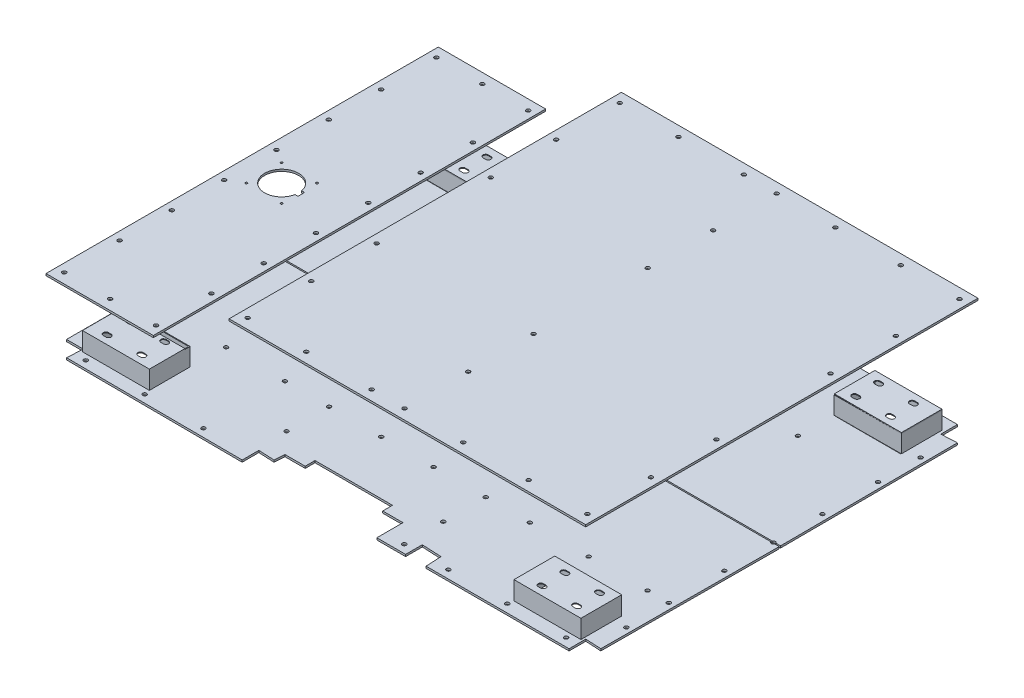
SolidWorks part; units mm, degrees
ref_plane "Front Plane" through (0, 0, 0) normal (0, 0, 1) x (1, 0, 0)
ref_plane "Top Plane" through (0, 0, 0) normal (0, 1, 0) x (1, 0, 0)
ref_plane "Right Plane" through (0, 0, 0) normal (1, 0, 0) x (0, 0, -1)
sketch "Sketch2" plane through (0, 422.0595, 0) normal (0, 1, 0) x (1, 0, 0)
  line L1 (715.0951, -383.2952) -> (690.8951, -384.4952)
  line L2 (690.8951, -384.4952) -> (690.8951, -359.0952)
  line L3 (690.8951, -359.0952) -> (466.2951, -359.0952)
  line L4 (466.2951, -359.0952) -> (465.0951, -383.2952)
  line L5 (465.0951, -383.2952) -> (440.8951, -384.4952)
  line L6 (440.8951, -384.4952) -> (440.8951, -359.0952)
  line L7 (440.8951, -359.0952) -> (390.8951, -359.0952)
  line L8 (390.8951, -359.0952) -> (390.8951, -399.0952)
  line L9 (410.8951, -483.6952) -> (410.8951, -384.4952) construction
  line L10 (390.8951, -399.0952) -> (216.2951, -399.0952)
  line L11 (196.2951, -384.4952) -> (196.2951, -483.6952) construction
  line L12 (216.2951, -399.0952) -> (215.0951, -383.2952)
  line L13 (215.0951, -383.2952) -> (190.8951, -384.4952)
  line L14 (190.8951, -384.4952) -> (190.8951, -359.0952)
  line L15 (190.8951, -359.0952) -> (-84.9049, -360.2952)
  line L16 (-84.9049, -360.2952) -> (-83.7049, -384.4952)
  line L17 (-83.7049, -384.4952) -> (-109.1049, -384.4952)
  line L18 (-109.1049, -384.4952) -> (-109.1049, -933.6952)
  line L19 (-109.1049, -933.6952) -> (-109.1049, -384.4952) construction
  line L20 (715.0951, -383.2952) -> (716.2951, -659.0952)
  line L21 (716.2951, -384.4952) -> (716.2951, -933.6952) construction
  line L22 (716.2951, -659.0952) -> (-109.1049, -659.0952) construction
  line L23 (715.0951, -934.8952) -> (716.2951, -659.0952)
  line L24 (-83.7049, -933.6952) -> (-109.1049, -933.6952)
  line L25 (-84.9049, -957.8952) -> (-83.7049, -933.6952)
  line L26 (190.8951, -959.0952) -> (-84.9049, -957.8952)
  line L27 (190.8951, -933.6952) -> (190.8951, -959.0952)
  line L28 (215.0951, -934.8952) -> (190.8951, -933.6952)
  line L29 (216.2951, -919.0952) -> (215.0951, -934.8952)
  line L30 (390.8951, -919.0952) -> (216.2951, -919.0952)
  line L31 (390.8951, -959.0952) -> (390.8951, -919.0952)
  line L32 (440.8951, -959.0952) -> (390.8951, -959.0952)
  line L33 (440.8951, -933.6952) -> (440.8951, -959.0952)
  line L34 (465.0951, -934.8952) -> (440.8951, -933.6952)
  line L35 (466.2951, -959.0952) -> (465.0951, -934.8952)
  line L36 (690.8951, -959.0952) -> (466.2951, -959.0952)
  line L37 (690.8951, -933.6952) -> (690.8951, -959.0952)
  line L38 (715.0951, -934.8952) -> (690.8951, -933.6952)
  line L39 (712.1088, -386.4469) -> (713.2907, -658.0952)
  line L40 (712.1088, -386.4469) -> (687.8951, -387.6476)
  line L41 (687.8951, -387.6476) -> (687.8951, -362.0952)
  line L42 (687.8951, -362.0952) -> (469.15, -362.0952)
  line L43 (469.15, -362.0952) -> (467.9569, -386.1569)
  line L44 (467.9569, -386.1569) -> (437.8951, -387.6476)
  line L45 (437.8951, -387.6476) -> (437.8951, -362.0952)
  line L46 (437.8951, -362.0952) -> (393.8951, -362.0952)
  line L47 (393.8951, -362.0952) -> (393.8951, -402.0952)
  line L48 (393.8951, -402.0952) -> (213.5143, -402.0952)
  line L49 (213.5143, -402.0952) -> (212.325, -386.4362)
  line L50 (212.325, -386.4362) -> (187.8951, -387.6476)
  line L51 (187.8951, -387.6476) -> (187.8951, -362.1082)
  line L52 (187.8951, -362.1082) -> (-81.7531, -363.2815)
  line L53 (-81.7531, -363.2815) -> (-80.5525, -387.4952)
  line L54 (-80.5525, -387.4952) -> (-106.1049, -387.4952)
  line L55 (-106.1049, -387.4952) -> (-106.1049, -658.0952)
  line L56 (-80.5525, -930.6952) -> (-106.1049, -930.6952)
  line L57 (-81.7531, -954.9089) -> (-80.5525, -930.6952)
  line L58 (187.8951, -956.0821) -> (-81.7531, -954.9089)
  line L59 (187.8951, -930.5427) -> (187.8951, -956.0821)
  line L60 (212.325, -931.7541) -> (187.8951, -930.5427)
  line L61 (213.5143, -916.0952) -> (212.325, -931.7541)
  line L62 (393.8951, -916.0952) -> (213.5143, -916.0952)
  line L63 (393.8951, -956.0952) -> (393.8951, -916.0952)
  line L64 (437.8951, -956.0952) -> (393.8951, -956.0952)
  line L65 (437.8951, -930.5427) -> (437.8951, -956.0952)
  line L66 (467.9569, -932.0334) -> (437.8951, -930.5427)
  line L67 (469.15, -956.0952) -> (467.9569, -932.0334)
  line L68 (687.8951, -956.0952) -> (469.15, -956.0952)
  line L69 (687.8951, -930.5427) -> (687.8951, -956.0952)
  line L70 (712.1088, -931.7434) -> (687.8951, -930.5427)
  line L71 (712.1088, -931.7434) -> (713.2907, -660.0952)
  line L72 (716.2951, -658.0952) -> (716.2907, -658.0952)
  line L73 (716.2951, -660.0952) -> (716.2907, -660.0952)
  line L74 (713.2907, -660.0952) -> (-106.1049, -660.0952)
  line L75 (713.2907, -658.0952) -> (-106.1049, -658.0952)
  line L76 (716.2951, -660.0952) -> (-109.1049, -660.0952) construction
  line L77 (-106.1049, -660.0952) -> (-106.1049, -930.6952)
  line L78 (716.2951, -658.0952) -> (-109.1049, -658.0952) construction
  line L80 (-106.1049, -387.4952) -> (-106.1049, -930.6952) construction
  line L81 (712.1088, -386.4469) -> (713.2951, -659.0952) construction
  line L82 (712.1088, -931.7434) -> (713.2951, -659.0952) construction
  circle A0 centre (-96.2049, -884.0952) radius 3 construction
  circle A1 centre (116.2951, -819.0952) radius 3 construction
  circle A2 centre (-63.7049, -819.0952) radius 3 construction
  circle A3 centre (-96.2049, -819.0952) radius 3 construction
  circle A4 centre (-96.2049, -884.0952) radius 3
  circle A5 centre (116.2951, -819.0952) radius 3
  circle A6 centre (-63.7049, -819.0952) radius 3
  circle A7 centre (-96.2049, -819.0952) radius 3
  circle A8 centre (-96.2049, -734.0952) radius 3 construction
  circle A9 centre (-96.2049, -734.0952) radius 3
  circle A10 centre (116.2951, -943.6952) radius 3 construction
  circle A11 centre (26.2951, -943.6952) radius 3 construction
  circle A12 centre (-63.7049, -943.6952) radius 3 construction
  circle A13 centre (116.2951, -943.6952) radius 3
  circle A14 centre (26.2951, -943.6952) radius 3
  circle A15 centre (-63.7049, -943.6952) radius 3
  circle A16 centre (-96.2049, -659.0952) radius 3 construction
  circle A17 centre (-96.2049, -659.0952) radius 3
  circle A18 centre (26.2951, -819.0952) radius 3 construction
  circle A19 centre (26.2951, -819.0952) radius 3
  circle A20 centre (343.5951, -819.0952) radius 3 construction
  circle A21 centre (183.7951, -734.0952) radius 3 construction
  circle A22 centre (263.5951, -819.0952) radius 3 construction
  circle A23 centre (183.7951, -819.0952) radius 3 construction
  circle A24 centre (183.7951, -884.0952) radius 3 construction
  circle A25 centre (343.5951, -819.0952) radius 3
  circle A26 centre (183.7951, -734.0952) radius 3
  circle A27 centre (263.5951, -819.0952) radius 3
  circle A28 centre (183.7951, -819.0952) radius 3
  circle A29 centre (183.7951, -884.0952) radius 3
  circle A30 centre (183.7951, -659.0952) radius 3 construction
  circle A31 centre (183.7951, -659.0952) radius 3
  circle A32 centre (26.2951, -499.0952) radius 3 construction
  circle A33 centre (26.2951, -499.0952) radius 3
  circle A34 centre (116.2951, -499.0952) radius 3 construction
  circle A35 centre (116.2951, -499.0952) radius 3
  circle A36 centre (183.7951, -499.0952) radius 3 construction
  circle A37 centre (183.7951, -499.0952) radius 3
  circle A38 centre (183.7951, -434.0952) radius 3 construction
  circle A39 centre (183.7951, -434.0952) radius 3
  circle A40 centre (116.2951, -374.4952) radius 3 construction
  circle A41 centre (116.2951, -374.4952) radius 3
  circle A42 centre (26.2951, -374.4952) radius 3 construction
  circle A43 centre (26.2951, -374.4952) radius 3
  circle A44 centre (-63.7049, -374.4952) radius 3 construction
  circle A45 centre (-63.7049, -374.4952) radius 3
  circle A46 centre (-96.2049, -434.0952) radius 3 construction
  circle A47 centre (-96.2049, -499.0952) radius 3 construction
  circle A48 centre (-96.2049, -584.0952) radius 3 construction
  circle A49 centre (-96.2049, -434.0952) radius 3
  circle A50 centre (-96.2049, -499.0952) radius 3
  circle A51 centre (-96.2049, -584.0952) radius 3
  circle A52 centre (-63.7049, -499.0952) radius 3 construction
  circle A53 centre (-63.7049, -499.0952) radius 3
  circle A54 centre (183.7951, -584.0952) radius 3 construction
  circle A55 centre (183.7951, -584.0952) radius 3
  circle A56 centre (423.3951, -584.0952) radius 3 construction
  circle A57 centre (423.3951, -584.0952) radius 3
  circle A58 centre (490.8951, -499.0952) radius 3 construction
  circle A59 centre (490.8951, -499.0952) radius 3
  circle A60 centre (580.8951, -499.0952) radius 3 construction
  circle A61 centre (580.8951, -499.0952) radius 3
  circle A62 centre (490.8951, -374.4952) radius 3 construction
  circle A63 centre (490.8951, -374.4952) radius 3
  circle A64 centre (580.8951, -374.4952) radius 3 construction
  circle A65 centre (580.8951, -374.4952) radius 3
  circle A66 centre (703.3951, -584.0952) radius 3 construction
  circle A67 centre (703.3951, -499.0952) radius 3 construction
  circle A68 centre (703.3951, -434.0952) radius 3 construction
  circle A69 centre (670.8951, -374.4952) radius 3 construction
  circle A70 centre (703.3951, -584.0952) radius 3
  circle A71 centre (703.3951, -499.0952) radius 3
  circle A72 centre (703.3951, -434.0952) radius 3
  circle A73 centre (670.8951, -374.4952) radius 3
  circle A74 centre (703.3951, -884.0952) radius 3 construction
  circle A75 centre (703.3951, -819.0952) radius 3 construction
  circle A76 centre (703.3951, -734.0952) radius 3 construction
  circle A77 centre (703.3951, -659.0952) radius 3 construction
  circle A78 centre (703.3951, -884.0952) radius 3
  circle A79 centre (703.3951, -819.0952) radius 3
  circle A80 centre (703.3951, -734.0952) radius 3
  circle A81 centre (703.3951, -659.0952) radius 3
  circle A82 centre (490.8951, -943.6952) radius 3 construction
  circle A83 centre (580.8951, -943.6952) radius 3 construction
  circle A84 centre (670.8951, -943.6952) radius 3 construction
  circle A85 centre (490.8951, -943.6952) radius 3
  circle A86 centre (580.8951, -943.6952) radius 3
  circle A87 centre (670.8951, -943.6952) radius 3
  circle A89 centre (580.8951, -819.0952) radius 3 construction
  circle A90 centre (670.8951, -819.0952) radius 3 construction
  circle A91 centre (580.8951, -819.0952) radius 3
  circle A92 centre (670.8951, -819.0952) radius 3
  circle A93 centre (490.8951, -819.0952) radius 3 construction
  circle A94 centre (490.8951, -819.0952) radius 3
  circle A95 centre (423.3951, -943.6952) radius 3 construction
  circle A96 centre (423.3951, -884.0952) radius 3 construction
  circle A97 centre (423.3951, -819.0952) radius 3 construction
  circle A98 centre (423.3951, -734.0952) radius 3 construction
  circle A99 centre (423.3951, -943.6952) radius 3
  circle A100 centre (423.3951, -884.0952) radius 3
  circle A101 centre (423.3951, -819.0952) radius 3
  circle A102 centre (423.3951, -734.0952) radius 3
  circle A103 centre (423.3951, -659.0952) radius 3 construction
  circle A104 centre (423.3951, -499.0952) radius 3 construction
  circle A105 centre (423.3951, -434.0952) radius 3 construction
  circle A106 centre (423.3951, -374.4952) radius 3 construction
  circle A107 centre (423.3951, -659.0952) radius 3
  circle A108 centre (423.3951, -499.0952) radius 3
  circle A109 centre (423.3951, -434.0952) radius 3
  circle A110 centre (423.3951, -374.4952) radius 3
  circle A111 centre (343.5951, -499.0952) radius 3 construction
  circle A113 centre (263.5951, -499.0952) radius 3 construction
  circle A114 centre (343.5951, -499.0952) radius 3
  circle A115 centre (263.5951, -499.0952) radius 3
  dimension "D1" = 40
  dimension "D2" = 3
  dimension "D3" = 1
  dimension "D4" = 1
extrude "Boss-Extrude1" add sketch "Sketch2" along normal blind 3 contours A107 L75 A81 L39 L40 L41 L42 L43 L44 L45 L46 L47 L48 L49 L50 L51 L52 L53 L54 L55 A17 A31 A115 A114 A110 A109 A108 A73 A72 A71 A70 A65 A63 A61 | A107 L74 A31 A17 L77 L56 L57 L58 L59 L60 L61 L62 L63 L64 L65 L66 L67 L68 L69 L70 L71 A81 A102 A101 A100 A99 A94 A92 A91 A87 A86 A85 A80 A79 region at (303.3396, 422.0595, 515.8841) region at (303.2947, 422.0595, 802.3042)
sketch "Sketch4" plane through (0, 602.0595, 0) normal (0, 1, 0) x (1, 0, 0)
  line L0 (716.2951, -359.0952) -> (170.8951, -359.0952) construction
  line L1 (170.8951, -359.0952) -> (170.8951, -959.0952) construction
  line L2 (170.8951, -933.6952) -> (170.8951, -384.4952) construction
  line L3 (716.2951, -959.0952) -> (716.2951, -359.0952) construction
  line L4 (170.8951, -959.0952) -> (716.2951, -959.0952) construction
  line L5 (716.2951, -359.0952) -> (170.8951, -359.0952)
  line L6 (170.8951, -359.0952) -> (170.8951, -959.0952)
  line L7 (170.8951, -933.6952) -> (170.8951, -384.4952)
  line L8 (716.2951, -959.0952) -> (716.2951, -359.0952)
  line L9 (170.8951, -959.0952) -> (716.2951, -959.0952)
  line L10 (170.8951, -359.0952) -> (716.2951, -959.0952) construction
  line L11 (170.8951, -959.0952) -> (716.2951, -359.0952) construction
  line L12 (443.5951, -659.0952) -> (716.2951, -659.0952) construction
  circle A1 centre (613.5951, -943.6952) radius 3 construction
  circle A2 centre (703.3951, -943.6952) radius 3 construction
  circle A3 centre (513.5951, -943.6952) radius 3 construction
  circle A4 centre (703.3951, -846.3952) radius 3 construction
  circle A5 centre (703.3951, -746.3952) radius 3 construction
  circle A6 centre (423.7951, -943.6952) radius 3 construction
  circle A7 centre (423.7951, -846.3952) radius 3 construction
  circle A8 centre (373.5951, -943.6952) radius 3 construction
  circle A9 centre (273.5951, -943.6952) radius 3 construction
  circle A10 centre (183.7951, -943.6952) radius 3 construction
  circle A11 centre (183.7951, -746.3952) radius 3 construction
  circle A12 centre (183.7951, -846.3952) radius 3 construction
  circle A13 centre (423.7951, -746.3952) radius 3 construction
  circle A14 centre (423.7951, -746.3952) radius 3
  circle A15 centre (183.7951, -846.3952) radius 3
  circle A16 centre (183.7951, -746.3952) radius 3
  circle A17 centre (183.7951, -943.6952) radius 3
  circle A18 centre (273.5951, -943.6952) radius 3
  circle A19 centre (373.5951, -943.6952) radius 3
  circle A20 centre (423.7951, -846.3952) radius 3
  circle A21 centre (423.7951, -943.6952) radius 3
  circle A22 centre (703.3951, -746.3952) radius 3
  circle A23 centre (703.3951, -846.3952) radius 3
  circle A24 centre (513.5951, -943.6952) radius 3
  circle A25 centre (703.3951, -943.6952) radius 3
  circle A26 centre (613.5951, -943.6952) radius 3
  circle A40 centre (613.5951, -374.4952) radius 3
  circle A41 centre (703.3951, -374.4952) radius 3
  circle A42 centre (513.5951, -374.4952) radius 3
  circle A43 centre (703.3951, -471.7952) radius 3
  circle A44 centre (703.3951, -571.7952) radius 3
  circle A45 centre (423.7951, -374.4952) radius 3
  circle A46 centre (423.7951, -471.7952) radius 3
  circle A47 centre (373.5951, -374.4952) radius 3
  circle A48 centre (273.5951, -374.4952) radius 3
  circle A49 centre (183.7951, -374.4952) radius 3
  circle A50 centre (183.7951, -571.7952) radius 3
  circle A51 centre (183.7951, -471.7952) radius 3
  circle A52 centre (423.7951, -571.7952) radius 3
extrude "Boss-Extrude2" add sketch "Sketch4" along normal blind 3 separate body contours L5 L6 L9 L8 | A49 | A48 | A47 | A46 | A51 | A50 | A52 | A45 | A42 | A40 | A41 | A43 | A44 | A22 | A14 | A16 | A15 | A18 | A19 | A20 | A21 | A24 | A26 | A23 | A25 | A17
sketch "Sketch6" plane through (0, 522.0595, 0) normal (0, 1, 0) x (1, 0, 0)
  line L0 (-109.1049, -959.0952) -> (-109.1049, -359.0952) construction
  line L1 (55.0951, -384.4952) -> (55.0951, -933.6952) construction
  line L2 (-109.1049, -959.0952) -> (-109.1049, -359.0952)
  line L3 (55.0951, -384.4952) -> (55.0951, -933.6952)
  line L4 (55.0951, -933.6952) -> (55.0951, -959.0952)
  line L5 (170.8951, -959.0952) -> (-109.1049, -959.0952) construction
  line L6 (55.0951, -959.0952) -> (-109.1049, -959.0952)
  line L7 (55.0951, -384.4952) -> (55.0951, -359.0952)
  line L8 (170.8951, -359.0952) -> (-109.1049, -359.0952) construction
  line L9 (55.0951, -359.0952) -> (-109.1049, -359.0952)
  line L10 (55.0951, -659.0952) -> (-109.1049, -659.0952) construction
  circle A0 centre (-96.6049, -943.6952) radius 3 construction
  circle A1 centre (-26.3999, -943.6952) radius 3 construction
  circle A2 centre (43.7951, -943.6952) radius 3 construction
  circle A3 centre (-96.6049, -943.6952) radius 3
  circle A4 centre (-26.3999, -943.6952) radius 3
  circle A5 centre (43.7951, -943.6952) radius 3
  circle A6 centre (-96.6049, -859.0952) radius 3 construction
  circle A7 centre (43.7951, -859.0952) radius 3 construction
  circle A8 centre (-96.6049, -859.0952) radius 3
  circle A9 centre (43.7951, -859.0952) radius 3
  circle A10 centre (43.7951, -699.0952) radius 3 construction
  circle A11 centre (-96.6049, -699.0952) radius 3 construction
  circle A12 centre (43.7951, -779.0952) radius 3 construction
  circle A13 centre (-96.6049, -779.0952) radius 3 construction
  circle A14 centre (43.7951, -699.0952) radius 3
  circle A15 centre (-96.6049, -699.0952) radius 3
  circle A16 centre (43.7951, -779.0952) radius 3
  circle A17 centre (-96.6049, -779.0952) radius 3
  circle A27 centre (-96.6049, -619.0952) radius 3
  circle A28 centre (-96.6049, -539.0952) radius 3
  circle A29 centre (43.7951, -539.0952) radius 3
  circle A30 centre (43.7951, -619.0952) radius 3
  circle A31 centre (43.7951, -459.0952) radius 3
  circle A32 centre (-96.6049, -459.0952) radius 3
  circle A33 centre (43.7951, -374.4952) radius 3
  circle A34 centre (-26.3999, -374.4952) radius 3
  circle A35 centre (-96.6049, -374.4952) radius 3
extrude "Boss-Extrude3" add sketch "Sketch6" along normal blind 3 separate body
sketch "Sketch9" plane through (0, 525.0595, 0) normal (0, 1, 0) x (1, 0, 0)
  line L0 (-48.7049, -659.0952) -> (-22.7049, -659.0952) construction
  line L1 (-48.7049, -654.0952) -> (-22.7049, -654.0952) construction
  line L2 (-48.7049, -664.0952) -> (-22.7049, -664.0952) construction
  line L3 (-23.1902, -654.0952) -> (-18.6902, -654.0952)
  line L4 (-18.6902, -654.0952) -> (-18.6902, -664.0952)
  line L5 (-18.6902, -664.0952) -> (-23.1902, -664.0952)
  arc A0 (-23.1902, -654.0952) -> (-23.1902, -664.0952) centre (-48.7049, -659.0952) ccw
  dimension "D1" = 52
  dimension "D4" = 4.5
  dimension "D2" = 5
  dimension "D3" = 5
extrude "Cut-Extrude1" cut sketch "Sketch9" against normal up to next (3 mm away)
sketch "Sketch10" plane through (0, 525.0595, 0) normal (0, 1, 0) x (1, 0, 0)
  circle A0 centre (-21.7049, -632.0952) radius 1.6
  circle A1 centre (-21.7049, -686.0952) radius 1.6
  circle A2 centre (-75.7049, -632.0952) radius 1.6
  circle A3 centre (-75.7049, -686.0952) radius 1.6
  dimension "D1" = 3.2
  dimension "D2" = 3.2
  dimension "D3" = 3.2
  dimension "D4" = 3.2
extrude "Cut-Extrude4" cut sketch "Sketch10" against normal up to next (3 mm away)
sketch "Sketch11" plane through (0, 422.0595, 0) normal (0, -1, 0) x (1, 0, 0)
  line L0 (244.2951, 916.0952) -> (244.2951, 901.0952)
  line L1 (393.8951, 916.0952) -> (213.5143, 916.0952) construction
  line L2 (244.2951, 901.0952) -> (362.8951, 901.0952)
  line L3 (362.8951, 901.0952) -> (362.8951, 916.0952)
  line L4 (244.2951, 402.0952) -> (362.8951, 402.0952)
  line L5 (410.8951, 933.6952) -> (410.8951, 834.4952) construction
  line L6 (196.2951, 959.0952) -> (196.2951, 834.4952) construction
  line L7 (196.2951, 659.0952) -> (436.2951, 659.0952) construction
  line L8 (196.2951, 809.0952) -> (196.2951, 509.0952) construction
  line L9 (436.2951, 809.0952) -> (436.2951, 509.0952) construction
  line L10 (362.8951, 417.0952) -> (362.8951, 402.0952)
  line L11 (244.2951, 417.0952) -> (362.8951, 417.0952)
  line L12 (244.2951, 402.0952) -> (244.2951, 417.0952)
  line L13 (244.2951, 916.0952) -> (362.8951, 916.0952)
  dimension "D1" = 15
  dimension "D2" = 48
  dimension "D3" = 48
extrude "Cut-Extrude5" cut sketch "Sketch11" against normal up to next (3 mm away)
sketch "Sketch13" plane through (0, 422.0595, 0) normal (0, -1, 0) x (1, 0, 0)
  line L1 (683.5951, 933.6952) -> (583.5951, 933.6952)
  line L3 (683.5951, 873.6952) -> (583.5951, 873.6952)
  line L4 (583.5951, 933.6952) -> (583.5951, 873.6952)
  line L7 (303.5951, 901.0952) -> (303.5951, 417.0952) construction
  line L22 (683.5951, 933.6952) -> (683.5951, 873.6952)
  line L24 (244.2951, 901.0952) -> (362.8951, 901.0952) construction
  line L25 (362.8951, 417.0952) -> (244.2951, 417.0952) construction
  line L26 (303.5951, 659.0952) -> (712.9729, 659.0952) construction
  line L29 (687.8951, 956.0952) -> (469.15, 956.0952) construction
  line L30 (683.5951, 384.4952) -> (683.5951, 444.4952)
  line L31 (583.5951, 384.4952) -> (583.5951, 444.4952)
  line L32 (683.5951, 444.4952) -> (583.5951, 444.4952)
  line L33 (683.5951, 384.4952) -> (583.5951, 384.4952)
  line L34 (-76.4049, 933.6952) -> (-76.4049, 873.6952)
  line L35 (23.5951, 933.6952) -> (23.5951, 873.6952)
  line L36 (-76.4049, 873.6952) -> (23.5951, 873.6952)
  line L37 (-76.4049, 933.6952) -> (23.5951, 933.6952)
  line L38 (-76.4049, 384.4952) -> (23.5951, 384.4952)
  line L39 (-76.4049, 444.4952) -> (23.5951, 444.4952)
  line L40 (23.5951, 384.4952) -> (23.5951, 444.4952)
  line L41 (-76.4049, 384.4952) -> (-76.4049, 444.4952)
  dimension "D1" = 60
  dimension "D2" = 100
  dimension "D3" = 22.4
  dimension "D4" = 380
extrude "Cut-Extrude6" cut sketch "Sketch13" against normal up to next (3 mm away)
sketch "Sketch15" plane through (0, 422.0595, 0) normal (0, -1, 0) x (1, 0, 0)
  line L0 (583.5951, 933.6952) -> (583.5951, 873.6952) construction
  line L1 (583.5951, 873.6952) -> (683.5951, 873.6952) construction
  line L2 (683.5951, 933.6952) -> (583.5951, 933.6952) construction
  line L3 (683.5951, 873.6952) -> (683.5951, 933.6952) construction
  line L4 (583.5951, 933.6952) -> (583.5951, 873.6952)
  line L5 (583.5951, 873.6952) -> (683.5951, 873.6952)
  line L6 (683.5951, 933.6952) -> (583.5951, 933.6952)
  line L7 (683.5951, 873.6952) -> (683.5951, 933.6952)
  line L8 (582.3951, 934.8952) -> (582.3951, 872.4952)
  line L9 (582.3951, 872.4952) -> (684.7951, 872.4952)
  line L10 (684.7951, 872.4952) -> (684.7951, 934.8952)
  line L11 (684.7951, 934.8952) -> (582.3951, 934.8952)
  line L13 (303.5951, 901.0952) -> (303.5951, 416.7343) construction
  line L14 (244.2951, 901.0952) -> (362.8951, 901.0952) construction
  line L15 (303.5951, 658.9147) -> (713.2907, 658.0952) construction
  line L16 (683.6879, 381.4114) -> (581.2887, 381.8211)
  line L17 (683.9375, 443.8109) -> (683.6879, 381.4114)
  line L18 (581.5384, 444.2206) -> (683.9375, 443.8109)
  line L19 (581.2887, 381.8211) -> (581.5384, 444.2206)
  line L20 (682.7327, 442.6157) -> (682.4927, 382.6162)
  line L21 (682.4927, 382.6162) -> (582.4935, 383.0163)
  line L22 (582.7335, 443.0158) -> (682.7327, 442.6157)
  line L23 (582.4935, 383.0163) -> (582.7335, 443.0158)
  line L24 (24.6967, 383.0163) -> (24.4566, 443.0158)
  line L25 (24.4566, 443.0158) -> (-75.5426, 442.6157)
  line L26 (-75.3025, 382.6162) -> (24.6967, 383.0163)
  line L27 (-75.5426, 442.6157) -> (-75.3025, 382.6162)
  line L28 (25.9015, 381.8211) -> (25.6518, 444.2206)
  line L29 (25.6518, 444.2206) -> (-76.7474, 443.8109)
  line L30 (-76.7474, 443.8109) -> (-76.4977, 381.4114)
  line L31 (-76.4977, 381.4114) -> (25.9015, 381.8211)
  line L32 (-77.6049, 934.8952) -> (24.7951, 934.8952)
  line L33 (-77.6049, 872.4952) -> (-77.6049, 934.8952)
  line L34 (24.7951, 872.4952) -> (-77.6049, 872.4952)
  line L35 (24.7951, 934.8952) -> (24.7951, 872.4952)
  line L36 (-76.4049, 873.6952) -> (-76.4049, 933.6952)
  line L37 (-76.4049, 933.6952) -> (23.5951, 933.6952)
  line L38 (23.5951, 873.6952) -> (-76.4049, 873.6952)
  line L39 (23.5951, 933.6952) -> (23.5951, 873.6952)
  dimension "D1" = 1.2
extrude "Boss-Extrude4" add sketch "Sketch15" against normal blind 27 from surface starting at face at (633.5951, 425.0595, 414.4952)
sketch "Sketch16" plane through (0, 452.0595, 0) normal (0, 1, 0) x (-1, 0, 0)
  line L0 (-684.7951, 934.8952) -> (-582.3951, 934.8952) construction
  line L1 (-684.7951, 934.8952) -> (-582.3951, 934.8952)
  line L2 (-684.7951, 934.8952) -> (-684.7951, 872.4952)
  line L3 (-684.7951, 872.4952) -> (-582.3951, 872.4952)
  line L4 (-582.3951, 934.8952) -> (-582.3951, 872.4952)
  line L5 (-684.7951, 872.4952) -> (-684.7951, 934.8952) construction
  line L6 (-582.3951, 934.8952) -> (-582.3951, 872.4952) construction
  line L7 (-582.3951, 872.4952) -> (-684.7951, 872.4952) construction
  line L8 (-581.5384, 444.2206) -> (-581.2887, 381.8211) construction
  line L9 (-683.9375, 443.8109) -> (-581.2887, 443.8109)
  line L10 (-683.9375, 443.8109) -> (-683.9375, 381.8211)
  line L11 (-683.9375, 381.8211) -> (-581.2887, 381.8211)
  line L12 (-581.2887, 443.8109) -> (-581.2887, 381.8211)
  line L13 (-581.2887, 381.8211) -> (-683.6879, 381.4114) construction
  line L14 (77.6049, 934.8952) -> (77.6049, 872.4952) construction
  line L15 (-24.7951, 934.8952) -> (77.6049, 934.8952)
  line L16 (-24.7951, 934.8952) -> (-24.7951, 880.4952)
  line L17 (-24.7951, 880.4952) -> (77.6049, 880.4952)
  line L18 (77.6049, 934.8952) -> (77.6049, 880.4952)
  line L19 (76.7474, 443.8109) -> (76.4977, 381.4114) construction
  line L20 (-25.6518, 444.2206) -> (76.4964, 444.2206)
  line L21 (-25.6518, 444.2206) -> (-25.6518, 381.0889)
  line L22 (-25.6518, 381.0889) -> (76.4964, 381.0889)
  line L23 (76.4964, 444.2206) -> (76.4964, 381.0889)
extrude "Boss-Extrude5" add sketch "Sketch16" along normal blind 1.2
sketch "Sketch18" plane through (0, 453.2595, 0) normal (0, 1, 0) x (1, 0, 0)
  line L0 (656.0609, -399.7221) -> (652.0609, -399.7381) construction
  line L1 (652.0289, -391.7381) -> (656.0289, -391.7221) construction
  line L2 (603.0293, -391.9342) -> (599.0294, -391.9502) construction
  line L3 (599.0614, -399.9501) -> (603.0613, -399.9341) construction
  line L4 (652.169, -426.7379) -> (656.1689, -426.7219) construction
  line L5 (656.2009, -434.7218) -> (652.201, -434.7378) construction
  line L6 (599.2014, -434.9498) -> (603.2014, -434.9338) construction
  line L7 (603.1694, -426.9339) -> (599.1694, -426.9499) construction
  line L8 (656.0609, -399.7221) -> (652.0609, -399.7381)
  line L9 (652.0289, -391.7381) -> (656.0289, -391.7221)
  line L10 (603.0293, -391.9342) -> (599.0294, -391.9502)
  line L11 (599.0614, -399.9501) -> (603.0613, -399.9341)
  line L12 (652.169, -426.7379) -> (656.1689, -426.7219)
  line L13 (656.2009, -434.7218) -> (652.201, -434.7378)
  line L14 (599.2014, -434.9498) -> (603.2014, -434.9338)
  line L15 (603.1694, -426.9339) -> (599.1694, -426.9499)
  arc A0 (652.0289, -391.7381) -> (652.0609, -399.7381) centre (652.0449, -395.7381) ccw construction
  arc A1 (656.0609, -399.7221) -> (656.0289, -391.7221) centre (656.0449, -395.7221) ccw construction
  arc A2 (603.0613, -399.9341) -> (603.0293, -391.9342) centre (603.0453, -395.9341) ccw construction
  arc A3 (599.0294, -391.9502) -> (599.0614, -399.9501) centre (599.0454, -395.9501) ccw construction
  arc A4 (652.169, -426.7379) -> (652.201, -434.7378) centre (652.185, -430.7378) ccw construction
  arc A5 (656.2009, -434.7218) -> (656.1689, -426.7219) centre (656.1849, -430.7218) ccw construction
  arc A6 (599.1694, -426.9499) -> (599.2014, -434.9498) centre (599.1854, -430.9499) ccw construction
  arc A7 (603.2014, -434.9338) -> (603.1694, -426.9339) centre (603.1854, -430.9339) ccw construction
  arc A8 (652.0289, -391.7381) -> (652.0609, -399.7381) centre (652.0449, -395.7381) ccw
  arc A9 (656.0609, -399.7221) -> (656.0289, -391.7221) centre (656.0449, -395.7221) ccw
  arc A10 (603.0613, -399.9341) -> (603.0293, -391.9342) centre (603.0453, -395.9341) ccw
  arc A11 (599.0294, -391.9502) -> (599.0614, -399.9501) centre (599.0454, -395.9501) ccw
  arc A12 (652.169, -426.7379) -> (652.201, -434.7378) centre (652.185, -430.7378) ccw
  arc A13 (656.2009, -434.7218) -> (656.1689, -426.7219) centre (656.1849, -430.7218) ccw
  arc A14 (599.1694, -426.9499) -> (599.2014, -434.9498) centre (599.1854, -430.9499) ccw
  arc A15 (603.2014, -434.9338) -> (603.1694, -426.9339) centre (603.1854, -430.9339) ccw
extrude "Cut-Extrude7" cut sketch "Sketch18" against normal through all
sketch "Sketch19" plane through (0, 453.2595, 0) normal (0, 1, 0) x (1, 0, 0)
  line L19 (614.0951, -882.6952) -> (610.0951, -882.6952) construction
  line L20 (610.0951, -890.6952) -> (614.0951, -890.6952) construction
  line L21 (663.0951, -882.6952) -> (667.0951, -882.6952) construction
  line L22 (667.0951, -890.6952) -> (663.0951, -890.6952) construction
  line L23 (614.0951, -917.6952) -> (610.0951, -917.6952) construction
  line L24 (610.0951, -925.6952) -> (614.0951, -925.6952) construction
  line L25 (663.0951, -917.6952) -> (667.0951, -917.6952) construction
  line L26 (667.0951, -925.6952) -> (663.0951, -925.6952) construction
  line L27 (614.0951, -882.6952) -> (610.0951, -882.6952)
  line L28 (610.0951, -890.6952) -> (614.0951, -890.6952)
  line L29 (663.0951, -882.6952) -> (667.0951, -882.6952)
  line L30 (667.0951, -890.6952) -> (663.0951, -890.6952)
  line L31 (614.0951, -917.6952) -> (610.0951, -917.6952)
  line L32 (610.0951, -925.6952) -> (614.0951, -925.6952)
  line L33 (663.0951, -917.6952) -> (667.0951, -917.6952)
  line L34 (667.0951, -925.6952) -> (663.0951, -925.6952)
  arc A19 (610.0951, -882.6952) -> (610.0951, -890.6952) centre (610.0951, -886.6952) ccw construction
  arc A20 (614.0951, -890.6952) -> (614.0951, -882.6952) centre (614.0951, -886.6952) ccw construction
  arc A21 (663.0951, -882.6952) -> (663.0951, -890.6952) centre (663.0951, -886.6952) ccw construction
  arc A22 (667.0951, -890.6952) -> (667.0951, -882.6952) centre (667.0951, -886.6952) ccw construction
  arc A23 (614.0951, -925.6952) -> (614.0951, -917.6952) centre (614.0951, -921.6952) ccw construction
  arc A24 (610.0951, -917.6952) -> (610.0951, -925.6952) centre (610.0951, -921.6952) ccw construction
  arc A25 (663.0951, -917.6952) -> (663.0951, -925.6952) centre (663.0951, -921.6952) ccw construction
  arc A26 (667.0951, -925.6952) -> (667.0951, -917.6952) centre (667.0951, -921.6952) ccw construction
  arc A27 (610.0951, -882.6952) -> (610.0951, -890.6952) centre (610.0951, -886.6952) ccw
  arc A28 (614.0951, -890.6952) -> (614.0951, -882.6952) centre (614.0951, -886.6952) ccw
  arc A29 (663.0951, -882.6952) -> (663.0951, -890.6952) centre (663.0951, -886.6952) ccw
  arc A30 (667.0951, -890.6952) -> (667.0951, -882.6952) centre (667.0951, -886.6952) ccw
  arc A31 (614.0951, -925.6952) -> (614.0951, -917.6952) centre (614.0951, -921.6952) ccw
  arc A32 (610.0951, -917.6952) -> (610.0951, -925.6952) centre (610.0951, -921.6952) ccw
  arc A33 (663.0951, -917.6952) -> (663.0951, -925.6952) centre (663.0951, -921.6952) ccw
  arc A34 (667.0951, -925.6952) -> (667.0951, -917.6952) centre (667.0951, -921.6952) ccw
extrude "Cut-Extrude8" cut sketch "Sketch19" against normal through all
sketch "Sketch21" plane through (0, 453.2595, 0) normal (0, 1, 0) x (1, 0, 0)
  line L0 (-50.9049, -917.6952) -> (-54.9049, -917.6952) construction
  line L1 (-54.9049, -925.6952) -> (-50.9049, -925.6952) construction
  line L2 (-50.9049, -882.6952) -> (-54.9049, -882.6952) construction
  line L3 (-54.9049, -890.6952) -> (-50.9049, -890.6952) construction
  line L4 (-1.9049, -882.6952) -> (2.0951, -882.6952) construction
  line L5 (2.0951, -890.6952) -> (-1.9049, -890.6952) construction
  line L6 (-1.9049, -917.6952) -> (2.0951, -917.6952) construction
  line L7 (2.0951, -925.6952) -> (-1.9049, -925.6952) construction
  line L8 (-50.9049, -917.6952) -> (-54.9049, -917.6952)
  line L9 (-54.9049, -925.6952) -> (-50.9049, -925.6952)
  line L10 (-50.9049, -882.6952) -> (-54.9049, -882.6952)
  line L11 (-54.9049, -890.6952) -> (-50.9049, -890.6952)
  line L12 (-1.9049, -882.6952) -> (2.0951, -882.6952)
  line L13 (2.0951, -890.6952) -> (-1.9049, -890.6952)
  line L14 (-1.9049, -917.6952) -> (2.0951, -917.6952)
  line L15 (2.0951, -925.6952) -> (-1.9049, -925.6952)
  arc A0 (-54.9049, -917.6952) -> (-54.9049, -925.6952) centre (-54.9049, -921.6952) ccw construction
  arc A1 (-50.9049, -925.6952) -> (-50.9049, -917.6952) centre (-50.9049, -921.6952) ccw construction
  arc A2 (-54.9049, -882.6952) -> (-54.9049, -890.6952) centre (-54.9049, -886.6952) ccw construction
  arc A3 (-50.9049, -890.6952) -> (-50.9049, -882.6952) centre (-50.9049, -886.6952) ccw construction
  arc A4 (-1.9049, -882.6952) -> (-1.9049, -890.6952) centre (-1.9049, -886.6952) ccw construction
  arc A5 (2.0951, -890.6952) -> (2.0951, -882.6952) centre (2.0951, -886.6952) ccw construction
  arc A6 (-1.9049, -917.6952) -> (-1.9049, -925.6952) centre (-1.9049, -921.6952) ccw construction
  arc A7 (2.0951, -925.6952) -> (2.0951, -917.6952) centre (2.0951, -921.6952) ccw construction
  arc A8 (-54.9049, -917.6952) -> (-54.9049, -925.6952) centre (-54.9049, -921.6952) ccw
  arc A9 (-50.9049, -925.6952) -> (-50.9049, -917.6952) centre (-50.9049, -921.6952) ccw
  arc A10 (-54.9049, -882.6952) -> (-54.9049, -890.6952) centre (-54.9049, -886.6952) ccw
  arc A11 (-50.9049, -890.6952) -> (-50.9049, -882.6952) centre (-50.9049, -886.6952) ccw
  arc A12 (-1.9049, -882.6952) -> (-1.9049, -890.6952) centre (-1.9049, -886.6952) ccw
  arc A13 (2.0951, -890.6952) -> (2.0951, -882.6952) centre (2.0951, -886.6952) ccw
  arc A14 (-1.9049, -917.6952) -> (-1.9049, -925.6952) centre (-1.9049, -921.6952) ccw
  arc A15 (2.0951, -925.6952) -> (2.0951, -917.6952) centre (2.0951, -921.6952) ccw
extrude "Cut-Extrude9" cut sketch "Sketch21" against normal through all
sketch "Sketch22" plane through (0, 453.2595, 0) normal (0, 1, 0) x (1, 0, 0)
  line L0 (-48.9788, -426.7219) -> (-52.9787, -426.7058) construction
  line L1 (-53.0107, -434.7058) -> (-49.0108, -434.7218) construction
  line L2 (-52.8707, -399.7061) -> (-48.8707, -399.7221) construction
  line L3 (-48.8387, -391.7221) -> (-52.8387, -391.7061) construction
  line L4 (0.0208, -426.9179) -> (4.0208, -426.9339) construction
  line L5 (3.9888, -434.9338) -> (-0.0112, -434.9178) construction
  line L6 (4.1288, -399.9341) -> (0.1289, -399.9181) construction
  line L7 (0.1609, -391.9182) -> (4.1608, -391.9342) construction
  line L8 (-48.9788, -426.7219) -> (-52.9787, -426.7058)
  line L9 (-53.0107, -434.7058) -> (-49.0108, -434.7218)
  line L10 (-52.8707, -399.7061) -> (-48.8707, -399.7221)
  line L11 (-48.8387, -391.7221) -> (-52.8387, -391.7061)
  line L12 (0.0208, -426.9179) -> (4.0208, -426.9339)
  line L13 (3.9888, -434.9338) -> (-0.0112, -434.9178)
  line L14 (4.1288, -399.9341) -> (0.1289, -399.9181)
  line L15 (0.1609, -391.9182) -> (4.1608, -391.9342)
  arc A0 (-52.9787, -426.7058) -> (-53.0107, -434.7058) centre (-52.9947, -430.7058) ccw construction
  arc A1 (-49.0108, -434.7218) -> (-48.9788, -426.7219) centre (-48.9948, -430.7218) ccw construction
  arc A2 (-52.8387, -391.7061) -> (-52.8707, -399.7061) centre (-52.8547, -395.7061) ccw construction
  arc A3 (-48.8707, -399.7221) -> (-48.8387, -391.7221) centre (-48.8547, -395.7221) ccw construction
  arc A4 (0.0208, -426.9179) -> (-0.0112, -434.9178) centre (0.0048, -430.9179) ccw construction
  arc A5 (3.9888, -434.9338) -> (4.0208, -426.9339) centre (4.0048, -430.9339) ccw construction
  arc A6 (0.1609, -391.9182) -> (0.1289, -399.9181) centre (0.1449, -395.9181) ccw construction
  arc A7 (4.1288, -399.9341) -> (4.1608, -391.9342) centre (4.1448, -395.9341) ccw construction
  arc A8 (-52.9787, -426.7058) -> (-53.0107, -434.7058) centre (-52.9947, -430.7058) ccw
  arc A9 (-49.0108, -434.7218) -> (-48.9788, -426.7219) centre (-48.9948, -430.7218) ccw
  arc A10 (-52.8387, -391.7061) -> (-52.8707, -399.7061) centre (-52.8547, -395.7061) ccw
  arc A11 (-48.8707, -399.7221) -> (-48.8387, -391.7221) centre (-48.8547, -395.7221) ccw
  arc A12 (0.0208, -426.9179) -> (-0.0112, -434.9178) centre (0.0048, -430.9179) ccw
  arc A13 (3.9888, -434.9338) -> (4.0208, -426.9339) centre (4.0048, -430.9339) ccw
  arc A14 (0.1609, -391.9182) -> (0.1289, -399.9181) centre (0.1449, -395.9181) ccw
  arc A15 (4.1288, -399.9341) -> (4.1608, -391.9342) centre (4.1448, -395.9341) ccw
extrude "Cut-Extrude10" cut sketch "Sketch22" against normal through all
